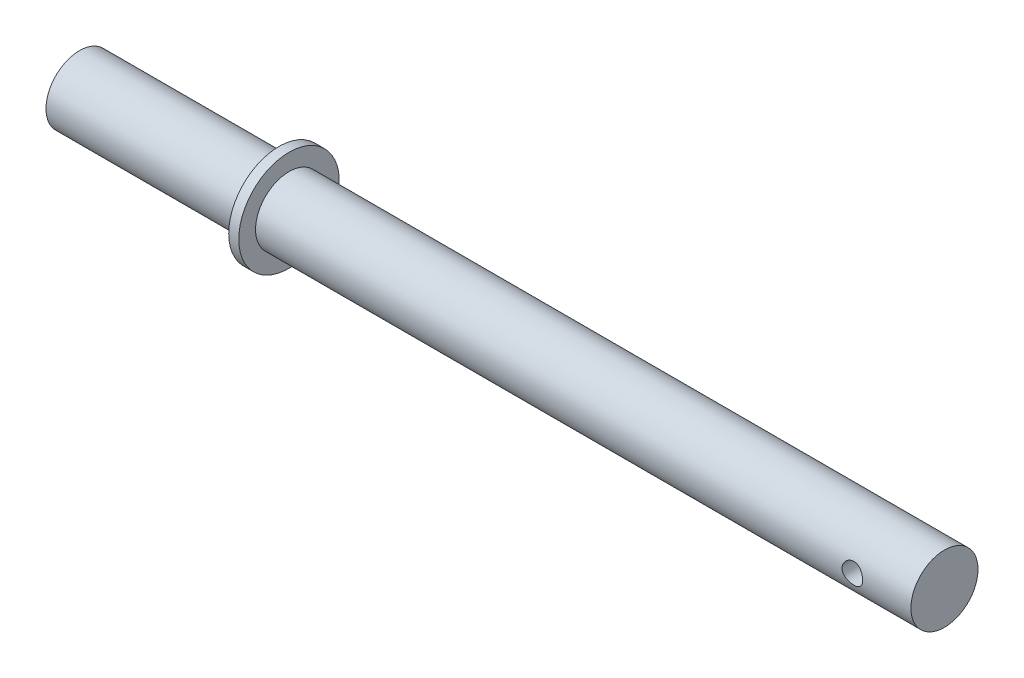
SolidWorks part; units mm, degrees
ref_plane "Alzado" through (0, 0, 0) normal (0, 0, 1) x (1, 0, 0)
ref_plane "Planta" through (0, 0, 0) normal (0, 1, 0) x (1, 0, 0)
ref_plane "Vista lateral" through (0, 0, 0) normal (1, 0, 0) x (0, 0, -1)
sketch "Croquis1" plane through (0, 0, 0) normal (1, 0, 0) x (0, 0, -1)
  circle A0 centre (0, 0) radius 10
  dimension "D1" = 20
extrude "Saliente-Extruir1" add sketch "Croquis1" along normal blind 258 from offset 8
ref_plane "Plano1" through (70.5, 0, 0) normal (-1, 0, 0) x (0, 0, 1)
sketch "Croquis2" plane through (70.5, 0, 0) normal (-1, 0, 0) x (0, 0, 1)
  circle A0 centre (0, 0) radius 15
  dimension "D1" = 30
extrude "Saliente-Extruir2" add sketch "Croquis2" along normal blind 3
sketch "Croquis3" plane through (0, 0, 0) normal (0, 0, 1) x (1, 0, 0)
  circle A0 centre (248.5, 0) radius 3.075
  dimension "D1" = 6.15
extrude "Cortar-Extruir1" cut sketch "Croquis3" against normal up to next and the other way up to next
